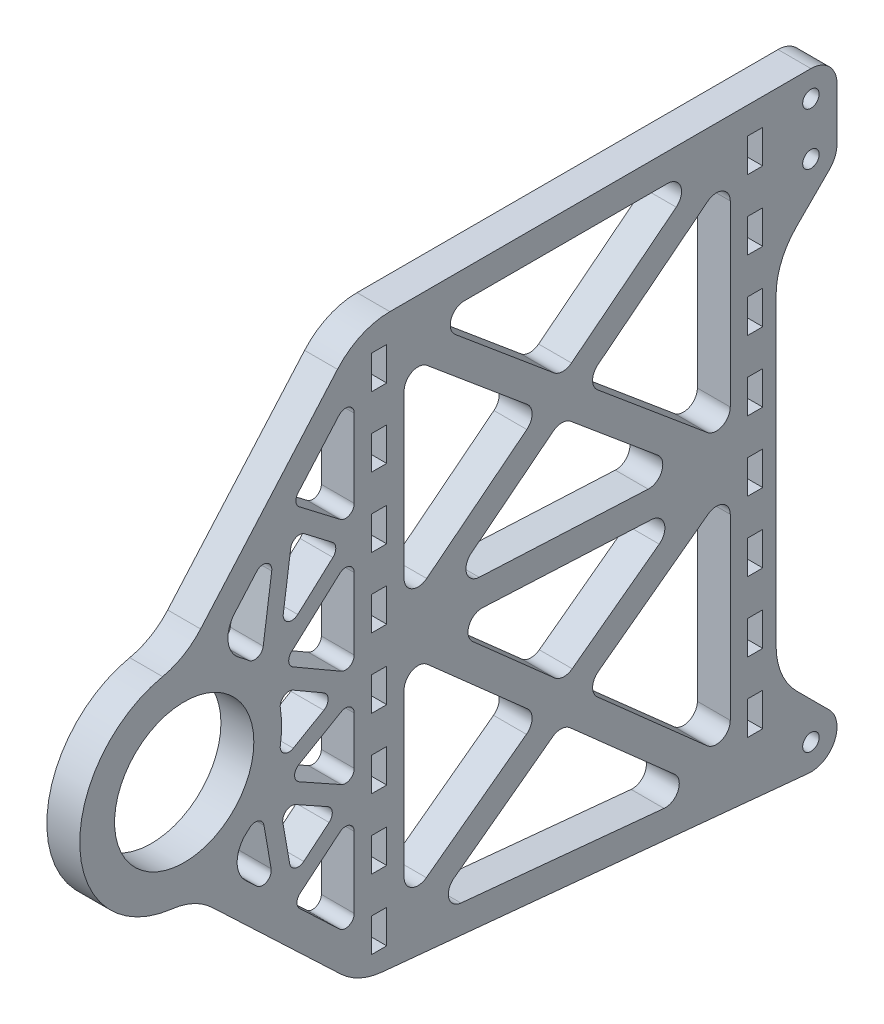
SolidWorks part; units mm, degrees
ref_plane "Front Plane" through (0, 0, 0) normal (0, 0, 1) x (1, 0, 0)
ref_plane "Top Plane" through (0, 0, 0) normal (0, 1, 0) x (1, 0, 0)
ref_plane "Right Plane" through (0, 0, 0) normal (1, 0, 0) x (0, 0, -1)
sketch "PlateGeometry" plane through (0, 0, 0) normal (1, 0, 0) x (0, 0, -1)
  line L1 (-38.1, -76.2) -> (38.1, -76.2) construction
  line L2 (-38.1, -76.2) -> (-38.1, 76.2) construction
  line L3 (-38.1, 76.2) -> (38.1, 76.2) construction
  line L4 (38.1, -76.2) -> (38.1, 76.2) construction
  line L5 (-38.1, -76.2) -> (38.1, 76.2) construction
  line L6 (-38.1, 76.2) -> (38.1, -76.2) construction
  line L11 (31.75, 76.2) -> (-31.75, 76.2) construction
  line L12 (31.75, 76.2) -> (31.75, -76.2) construction
  line L13 (31.75, -76.2) -> (-31.75, -76.2) construction
  line L14 (-31.75, 76.2) -> (-31.75, -76.2) construction
  line L15 (31.75, 76.2) -> (-31.75, -76.2) construction
  line L16 (31.75, -76.2) -> (-31.75, 76.2) construction
  point P0 (0, 0)
  point P9 (0, 0)
  line B0 (-35.7923, -66.6761) -> (-32.7923, -66.6739)
  line B1 (-35.7923, -66.6761) -> (-35.7877, -73.0261)
  line B2 (-35.7877, -73.0261) -> (-32.7877, -73.0239)
  line B3 (-32.7923, -66.6739) -> (-32.7877, -73.0239)
  line B4 (-35.7923, -66.6761) -> (-32.7877, -73.0239) construction
  line B5 (-35.7877, -73.0261) -> (-32.7923, -66.6739) construction
  line B6 (-35.7923, -53.9761) -> (-32.7923, -53.9739)
  line B7 (-35.7923, -53.9761) -> (-35.7877, -60.3261)
  line B8 (-35.7877, -60.3261) -> (-32.7877, -60.3239)
  line B9 (-32.7923, -53.9739) -> (-32.7877, -60.3239)
  line B10 (-35.7877, -60.3261) -> (-32.7923, -53.9739) construction
  line B11 (-35.7923, -41.2761) -> (-32.7923, -41.2739)
  line B12 (-35.7923, -41.2761) -> (-35.7877, -47.6261)
  line B13 (-35.7877, -47.6261) -> (-32.7877, -47.6239)
  line B14 (-32.7923, -41.2739) -> (-32.7877, -47.6239)
  line B15 (-35.7923, -41.2761) -> (-32.7877, -47.6239) construction
  line B16 (-35.7877, -47.6261) -> (-32.7923, -41.2739) construction
  line B17 (-35.7923, -28.5761) -> (-32.7923, -28.5739)
  line B18 (-35.7877, -34.9261) -> (-32.7877, -34.9239)
  line B19 (-32.7923, -28.5739) -> (-32.7877, -34.9239)
  line B20 (-35.7923, -15.8761) -> (-35.7877, -22.2261)
  line B21 (-32.7923, -15.8739) -> (-32.7877, -22.2239)
  line B22 (-35.7923, 9.5239) -> (-32.7923, 9.5261)
  line B23 (-32.7923, 9.5261) -> (-32.7877, 3.1761)
  line B24 (-35.7923, 9.5239) -> (-32.7877, 3.1761) construction
  line B25 (-35.7923, 22.2239) -> (-35.7877, 15.8739)
  line B26 (-35.7923, 34.9239) -> (-35.7877, 28.5739)
  line B27 (-35.7923, 47.6239) -> (-35.7877, 41.2739)
  line B28 (-35.7877, 41.2739) -> (-32.7923, 47.6261) construction
  line B29 (32.7886, -66.6757) -> (32.7914, -73.0257)
  line B30 (32.7914, -73.0257) -> (35.7914, -73.0243)
  line B31 (35.7886, -66.6743) -> (35.7914, -73.0243)
  line B32 (32.7886, -66.6757) -> (35.7914, -73.0243) construction
  line B33 (32.7914, -73.0257) -> (35.7886, -66.6743) construction
  line B34 (32.7886, -53.9757) -> (35.7886, -53.9743)
  line B35 (35.7886, -53.9743) -> (35.7914, -60.3243)
  line B36 (32.7914, -47.6257) -> (35.7914, -47.6243)
  line B37 (35.7886, -41.2743) -> (35.7914, -47.6243)
  line B38 (32.7886, -41.2757) -> (35.7914, -47.6243) construction
  line B39 (32.7886, -28.5757) -> (35.7914, -34.9243) construction
  line B40 (32.7886, -15.8757) -> (32.7914, -22.2257)
  line B41 (32.7886, -3.1757) -> (35.7914, -9.5243) construction
  line B42 (32.7914, -9.5257) -> (35.7886, -3.1743) construction
  line B43 (32.7886, 9.5243) -> (35.7886, 9.5257)
  line B44 (32.7886, 9.5243) -> (32.7914, 3.1743)
  line B45 (32.7914, 3.1743) -> (35.7914, 3.1757)
  line B46 (32.7886, 9.5243) -> (35.7914, 3.1757) construction
  line B47 (32.7886, 22.2243) -> (32.7914, 15.8743)
  line B48 (35.7886, 22.2257) -> (35.7914, 15.8757)
  line B49 (32.7886, 22.2243) -> (35.7914, 15.8757) construction
  line B50 (32.7914, 15.8743) -> (35.7886, 22.2257) construction
  line B51 (32.7914, 41.2743) -> (35.7914, 41.2757)
  line B52 (35.7886, 47.6257) -> (35.7914, 41.2757)
  line B53 (32.7886, 60.3243) -> (32.7914, 53.9743)
  line B54 (35.7886, 60.3257) -> (35.7914, 53.9757)
  line B55 (32.7886, 73.0243) -> (32.7914, 66.6743)
  line B56 (35.7886, 73.0257) -> (35.7914, 66.6757)
  line B57 (32.7914, 66.6743) -> (35.7886, 73.0257) construction
  circle B58 centre (-37.3063, -73.025) radius 5.5563 construction
  circle B59 centre (-37.3063, -73.025) radius 6.8263 construction
  circle B60 centre (-44.9262, -53.975) radius 5.5563 construction
  circle B61 centre (-44.9262, -53.975) radius 6.8263 construction
  dimension "D11" = 63.5
  dimension "D12" = 3.175
  dimension "D1" = 76.2
  dimension "D2" = 152.4
  dimension "D4" = 3.81
  dimension "D5" = 6.35
  dimension "D6" = 12.7
  dimension "D7" = 6.35
  dimension "D8" = 3.81
  dimension "D10" = 12.7
  dimension "D13" = 19.05
  dimension "D14" = 7.62
  dimension "D3" = 12
  dimension "D9" = 12
sketch_block_instance "SlotOutline-1"
sketch_block "SlotOutline" parameters "D1"=18.06, "D2"=7.2935
sketch_block_instance "SlotOutline-2"
sketch_block_instance "SlotOutline-3"
sketch_block_instance "SlotOutline-4"
sketch_block_instance "SlotOutline-5"
sketch_block_instance "SlotOutline-6"
sketch_block_instance "SlotOutline-7"
sketch_block_instance "SlotOutline-8"
sketch_block_instance "SlotOutline-9"
sketch_block_instance "SlotOutline-10"
sketch_block_instance "SlotOutline-11"
sketch_block_instance "SlotOutline-12"
sketch_block_instance "SlotOutline-13"
sketch_block_instance "SlotOutline-14"
sketch_block_instance "SlotOutline-15"
sketch_block_instance "SlotOutline-16"
sketch_block_instance "SlotOutline-17"
sketch_block_instance "SlotOutline-18"
sketch_block_instance "SlotOutline-19"
sketch_block_instance "SlotOutline-20"
sketch_block_instance "SlotOutline-21"
sketch_block_instance "SlotOutline-22"
sketch_block_instance "SlotOutline-23"
sketch_block_instance "SlotOutline-24"
sketch_block_instance "PulleyOutline-1"
sketch_block "PulleyOutline" parameters "D1"=11.1125, "D2"=13.6525
sketch_block_instance "PulleyOutline-2"
sketch "MotorGeometry" plane through (0, 0, 0) normal (1, 0, 0) x (0, 0, -1)
  line L0 (-83.2734, 1.775) -> (-83.2734, 49.025) construction
  line L3 (-50.2786, -55.4665) -> (-63.8121, -13.9087) construction
  line L4 (-41.2645, -76.9242) -> (-75.3216, -19.0975) construction
  line L5 (-38.1, -76.2) -> (-38.1, 76.2) construction
  line L6 (-38.1, -76.2) -> (38.1, -76.2) construction
  line L7 (38.1, -76.2) -> (38.1, 76.2) construction
  line L8 (-83.2734, 17.65) -> (-69.85, 9.9) construction
  line L9 (-69.85, 9.9) -> (-56.4266, 17.65) construction
  line L10 (-56.4266, 17.65) -> (-56.4266, 33.15) construction
  line L11 (-56.4266, 33.15) -> (-69.85, 40.9) construction
  line L12 (-69.85, 40.9) -> (-83.2734, 33.15) construction
  line L13 (-83.2734, 33.15) -> (-83.2734, 17.65) construction
  line L14 (-86.2734, 1.775) -> (-86.2734, 49.025)
  line L15 (-80.2734, 1.775) -> (-80.2734, 49.025)
  line L16 (-56.4266, 1.775) -> (-56.4266, 49.025) construction
  line L17 (-59.4266, 1.775) -> (-59.4266, 49.025)
  line L18 (-53.4266, 1.775) -> (-53.4266, 49.025)
  line L19 (-69.85, 8.3125) -> (-69.85, 47.25) construction
  line L20 (-72.85, 8.3125) -> (-72.85, 47.25)
  line L21 (-66.85, 8.3125) -> (-66.85, 47.25)
  circle A0 centre (44.45, -66.675) radius 1.5
  circle A1 centre (-69.85, -15.875) radius 11
  circle A5 centre (-69.85, -15.875) radius 30 construction
  circle A6 centre (-69.85, -15.875) radius 6.35 construction
  circle A7 centre (-44.9262, -53.975) radius 5.5562 construction
  circle A8 centre (-37.3063, -73.025) radius 5.5562 construction
  circle A9 centre (-69.85, -15.875) radius 25.5 construction
  circle A10 centre (-69.85, 25.4) radius 16 construction
  circle A11 centre (-69.85, 25.4) radius 11.5 construction
  circle A12 centre (-69.85, 25.4) radius 13.4234 construction
  arc A13 (-86.2734, 1.775) -> (-80.2734, 1.775) centre (-83.2734, 1.775) ccw
  arc A14 (-80.2734, 49.025) -> (-86.2734, 49.025) centre (-83.2734, 49.025) ccw
  arc A15 (-59.4266, 1.775) -> (-53.4266, 1.775) centre (-56.4266, 1.775) ccw
  arc A16 (-53.4266, 49.025) -> (-59.4266, 49.025) centre (-56.4266, 49.025) ccw
  arc A17 (-72.85, 8.3125) -> (-66.85, 8.3125) centre (-69.85, 8.3125) ccw
  arc A18 (-66.85, 47.25) -> (-72.85, 47.25) centre (-69.85, 47.25) ccw
  point P29 (-83.2734, 25.4)
  point P39 (-56.4266, 25.4)
  point P46 (-69.85, 27.7812)
  dimension "D1" = 22
  dimension "D4" = 60
  dimension "D5" = 12.7
  dimension "D7" = 4.5
  dimension "D8" = 32
  dimension "D9" = 4.5
  dimension "D13" = 3
  dimension "D3" = 6
  dimension "D2" = 31
  dimension "D6" = 38.1
  dimension "D10" = 31.75
  dimension "D11" = 9.525
  dimension "D12" = 6.35
  dimension "D14" = 15.875
  dimension "D15" = 1.5875
  dimension "D16" = 15.875
  dimension "D17" = 6.35
  dimension "D18" = 41.275
sketch "Sketch4" plane through (0, 0, 0) normal (1, 0, 0) x (0, 0, -1)
  line L0 (49.2125, 25.4) -> (49.2125, 34.925)
  line L1 (47.8176, 22.0324) -> (38.1, 12.3148)
  line L2 (-30.48, -50.8) -> (-38.1, -50.8) construction
  line L3 (-30.48, -50.8) -> (-30.48, -63.5) construction
  line L4 (-30.48, -63.5) -> (-38.1, -63.5) construction
  line L5 (-38.1, -50.8) -> (-38.1, -63.5) construction
  line L6 (-30.48, -50.8) -> (-38.1, -63.5) construction
  line L7 (-30.48, -63.5) -> (-38.1, -50.8) construction
  line L8 (38.1, 12.3148) -> (38.1, -53.5898)
  line L9 (38.1, -53.5898) -> (47.8176, -63.3074)
  line L10 (38.1, -76.2) -> (38.1, 76.2) construction
  line L11 (43.9929, -71.4155) -> (-38.1, -63.5)
  line L12 (-38.1, -63.5) -> (-68.2893, -34.861)
  line L13 (-70.0557, 3.1739) -> (-38.1, 39.6875)
  line L14 (-38.1, -76.2) -> (-38.1, 76.2) construction
  line L15 (-38.1, 39.6875) -> (44.45, 39.6875)
  line L17 (-83.2734, 1.775) -> (-83.2734, 58.55) construction
  line L18 (-86.2734, 1.775) -> (-86.2734, 58.55) construction
  line L19 (-80.2734, 1.775) -> (-80.2734, 58.55) construction
  line L20 (-69.85, 8.3125) -> (-69.85, 53.6) construction
  line L21 (-72.85, 8.3125) -> (-72.85, 53.6) construction
  line L22 (-66.85, 8.3125) -> (-66.85, 53.6) construction
  line L23 (-56.4266, 1.775) -> (-56.4266, 58.55) construction
  line L24 (-59.4266, 1.775) -> (-59.4266, 58.55) construction
  line L25 (-53.4266, 1.775) -> (-53.4266, 58.55) construction
  circle A0 centre (44.45, 25.4) radius 1.5
  circle A1 centre (44.45, 34.925) radius 1.5
  circle A2 centre (44.45, -66.675) radius 4.7625 construction
  circle A3 centre (44.45, 25.4) radius 4.7625 construction
  circle A4 centre (44.45, 34.925) radius 4.7625 construction
  circle A5 centre (-69.85, -15.875) radius 12.7
  arc A6 (43.9929, -71.4155) -> (47.8176, -63.3074) centre (44.45, -66.675) ccw
  circle A7 centre (-69.85, -15.875) radius 19.05
  arc A8 (47.8176, 22.0324) -> (49.2125, 25.4) centre (44.45, 25.4) ccw
  arc A9 (49.2125, 34.925) -> (44.45, 39.6875) centre (44.45, 34.925) ccw
  circle A10 centre (44.45, -66.675) radius 1.5
  arc A11 (-86.2734, 1.775) -> (-80.2734, 1.775) centre (-83.2734, 1.775) ccw construction
  arc A12 (-80.2734, 58.55) -> (-86.2734, 58.55) centre (-83.2734, 58.55) ccw construction
  arc A13 (-72.85, 8.3125) -> (-66.85, 8.3125) centre (-69.85, 8.3125) ccw construction
  arc A14 (-66.85, 53.6) -> (-72.85, 53.6) centre (-69.85, 53.6) ccw construction
  arc A15 (-59.4266, 1.775) -> (-53.4266, 1.775) centre (-56.4266, 1.775) ccw construction
  arc A16 (-53.4266, 58.55) -> (-59.4266, 58.55) centre (-56.4266, 58.55) ccw construction
  arc A17 (-72.85, 24.1875) -> (-66.85, 24.1875) centre (-69.85, 24.1875) cw construction
  arc A18 (-72.85, 33.3625) -> (-66.85, 33.3625) centre (-69.85, 33.3625) ccw construction
  point P12 (-34.29, -57.15)
  point P36 (-83.2734, 30.1625)
  point P41 (-65.6393, 2.7038)
  point P42 (-71.0229, -34.8889)
  point P47 (-69.85, 30.9562)
  point P55 (-56.4266, 30.1625)
  dimension "D1" = 3
  dimension "D4" = 9.525
  dimension "D9" = 25.4
  dimension "D10" = 38.1
  dimension "D11" = 6
  dimension "D14" = 3.175
  dimension "D2" = 9.525
  dimension "D3" = 101.6
  dimension "D5" = 3.81
  dimension "D6" = 12.7
  dimension "D7" = 45
  dimension "D8" = 45
  dimension "D12" = 12.7
  dimension "D13" = 25.4
  dimension "D15" = 15.875
extrude "Boss-Extrude1" add sketch "Sketch4" along normal mid plane 6 contours L0 A9 L13 A7 L12 L11 A6 L9 L8 L1 A8 A0 A1 | A7 A5 | L24 A15 L25 L13 | L13 A13 L22 region at (0, -13.2133, 6.0048) region at (0, -2.7151, 56.8315)
sketch "Sketch5" plane through (3, 0, 0) normal (1, 0, 0) x (0, 0, -1)
  line B0 (35.665, -54.102) -> (32.915, -54.102)
  line B1 (35.665, -54.102) -> (35.665, -60.198)
  line B2 (35.665, -60.198) -> (32.915, -60.198)
  line B3 (32.915, -54.102) -> (32.915, -60.198)
  line B4 (35.665, -54.102) -> (32.915, -60.198) construction
  line B5 (35.665, -60.198) -> (32.915, -54.102) construction
  line B6 (-32.915, -54.102) -> (-35.665, -54.102)
  line B7 (-32.915, -54.102) -> (-32.915, -60.198)
  line B8 (-32.915, -60.198) -> (-35.665, -60.198)
  line B9 (-35.665, -54.102) -> (-35.665, -60.198)
  line B10 (-32.915, -54.102) -> (-35.665, -60.198) construction
  line B11 (-32.915, -60.198) -> (-35.665, -54.102) construction
sketch_block_instance "Slot-1"
sketch_block "Slot" parameters "D1"=11.2845, "D2"=5.6739
sketch_block_instance "Slot-2"
extrude "LowerSlot" cut sketch "Sketch5" against normal through all both and the other way through all contours B0 B3 B2 B1 region at (3, -57.15, -34.29)
extrude "UpperSlot" cut sketch "Sketch5<3>" against normal through all both and the other way through all contours B6 B9 B8 B7 region at (3, -57.15, 34.29)
sketch "Sketch5<3>" plane through (3, 0, 0) normal (1, 0, 0) x (0, 0, -1) same geometry as "Sketch5"
pattern_linear "LowerSlots" count 8 spacing 12.7 along (0, 1, 0) of "LowerSlot"
pattern_linear "UpperSlots" count 8 spacing 12.7 along (0, 1, 0) of "UpperSlot"
sketch "Sketch6" plane through (3, 0, 0) normal (1, 0, 0) x (0, 0, -1)
  line L0 (-38.84, 7.4417) -> (-54.5614, -6.7982) construction
  line L1 (-54.5614, -6.7982) -> (-38.84, -15.875) construction
  line L2 (-38.84, -15.875) -> (-54.5614, -24.9518) construction
  line L3 (-54.5614, -24.9518) -> (-38.84, -33.7118) construction
  line L4 (-38.84, -15.875) -> (-52.07, -15.875) construction
  line L5 (-51.2473, 16.9514) -> (-54.5614, -6.7982) construction
  line L6 (-54.5614, -24.9518) -> (-51.2473, -44.0256) construction
  line L8 (29.74, -64.9377) -> (29.74, 34.6075)
  line L9 (-29.74, -59.2025) -> (-29.74, 34.6075)
  line L10 (-38.84, 31.1284) -> (-38.84, -55.7958)
  line L11 (-32.915, -54.102) -> (-32.915, -60.198) construction
  line L12 (-35.665, -54.102) -> (-35.665, -60.198) construction
  line L13 (32.915, -54.102) -> (32.915, -60.198) construction
  line L14 (29.74, -15.1651) -> (-29.74, -12.2975) construction
  line L15 (29.74, -64.9377) -> (-29.74, -12.2975) construction
  line L16 (44.1325, 25.5315) -> (44.1325, 34.6075)
  line L17 (44.1325, 34.6075) -> (-35.7952, 34.6075)
  line L18 (-35.7952, 34.6075) -> (-67.873, -2.0456)
  line L19 (-66.5997, -29.4616) -> (-35.8722, -58.6113)
  line L20 (-35.8722, -58.6113) -> (43.6001, -66.2741)
  line L21 (43.6001, -66.2741) -> (33.02, -55.694)
  line L22 (33.02, -55.694) -> (33.02, 14.419)
  line L23 (33.02, 14.419) -> (44.1325, 25.5315)
  line L24 (44.1325, 25.5315) -> (44.1325, 34.6075)
  line L25 (44.1325, 34.6075) -> (-35.7952, 34.6075)
  line L26 (-35.7952, 34.6075) -> (-67.873, -2.0456)
  line L27 (-66.5997, -29.4616) -> (-35.8722, -58.6113)
  line L28 (-35.8722, -58.6113) -> (43.6001, -66.2741)
  line L29 (43.6001, -66.2741) -> (33.02, -55.694)
  line L30 (33.02, -55.694) -> (33.02, 14.419)
  line L31 (33.02, 14.419) -> (44.1325, 25.5315)
  line L32 (-29.74, -12.2975) -> (29.74, 34.6075) construction
  line L33 (29.74, -15.1651) -> (-29.74, 34.6075) construction
  line L34 (-29.74, -59.2025) -> (29.74, -15.1651) construction
  line L35 (-51.2473, -44.0256) -> (-38.84, -33.7118) construction
  line L39 (-38.84, 7.4417) -> (-51.2473, 16.9514) construction
  line L44 (-56.695, -21.9456) -> (-52.3418, -46.9999)
  line L45 (-52.3418, -46.9999) -> (-36.0444, -33.4522)
  line L46 (-56.695, -21.9456) -> (-36.0444, -33.4522)
  line L47 (-55.3552, -8.1731) -> (-42.015, -15.875)
  line L48 (-42.015, -15.875) -> (-55.3552, -23.5769)
  line L49 (-52.4432, 19.8681) -> (-56.7383, -10.9119)
  line L50 (-36.363, 7.5434) -> (-52.4432, 19.8681)
  line L51 (-36.363, 7.5434) -> (-56.7383, -10.9119)
  line L52 (-52.4278, -27.9579) -> (-50.1528, -41.0514)
  line L53 (-50.1528, -41.0514) -> (-41.6356, -33.9713)
  line L54 (-52.4278, -27.9579) -> (-41.6356, -33.9713)
  line L55 (-53.7677, -5.4234) -> (-35.665, -15.875)
  line L56 (-35.665, -15.875) -> (-53.7677, -26.3266)
  line L57 (-50.0515, 14.0346) -> (-52.3845, -2.6846)
  line L58 (-41.317, 7.3401) -> (-50.0515, 14.0346)
  line L59 (-41.317, 7.3401) -> (-52.3845, -2.6846)
  line L60 (28.0566, -66.8398) -> (-31.4234, -14.1996)
  line L61 (-31.3128, -10.303) -> (28.1672, 36.602)
  line L62 (28.11, -17.113) -> (-31.37, 32.6595)
  line L63 (-31.2514, -57.1611) -> (28.2286, -13.1237)
  line L64 (29.6177, -17.7021) -> (-29.8623, -14.8346)
  line L65 (31.4234, -63.0356) -> (-28.0566, -10.3954)
  line L66 (-28.1672, -14.292) -> (31.3128, 32.613)
  line L67 (31.37, -13.2171) -> (-28.11, 36.5555)
  line L68 (-28.2286, -61.2439) -> (31.2514, -17.2065)
  line L69 (29.8623, -12.628) -> (-29.6177, -9.7605)
  arc A5 (-58.6124, -37.0388) -> (-58.3903, -29.4693) centre (-55.1161, -33.3533) cw
  circle A6 centre (-69.85, -15.875) radius 17.78
  circle A7 centre (-69.85, -15.875) radius 17.78
  arc A8 (-67.873, -2.0456) -> (-66.5997, -29.4616) centre (-69.85, -15.875) ccw
  arc A9 (-67.873, -2.0456) -> (-66.5997, -29.4616) centre (-69.85, -15.875) ccw
  arc A10 (-59.6996, -1.2771) -> (-60.6223, 6.2393) centre (-56.7995, 2.8937) cw
  point P18 (0, 0)
  point P41 (-51.2473, 16.9514)
  dimension "D6" = 5.08
  dimension "D2" = 3.175
  dimension "D3" = 3.175
  dimension "D4" = 3.175
  dimension "D7" = 60
  dimension "D1" = 5.08
  dimension "D5" = 5.08
  dimension "D8" = 1.5875
  dimension "D9" = 1.5875
  dimension "D10" = 2.54
  dimension "D11" = 2.54
extrude "Cut-Extrude1" cut sketch "Sketch6" against normal through all both and the other way through all contours L45 L27 L10 | L54 L52 L53 | L10 L56 L46 | A7 A5 L27 L44 | A7 L48 L47 | L51 L55 L10 | L59 L58 L57 | A10 A7 L49 L26 | L50 L10 L26 region at (3, -45.566, 42.5892) region at (3, -24.8433, 43.008) region at (3, -34.2808, 56.7363) region at (3, -5.0849, 43.1871) region at (3, 19.5729, 42.6265) region at (3, -15.875, 48.9797) region at (3, 4.3105, 57.3434) region at (3, -34.3269, 48.0721) region at (3, 6.23, 47.9176)
extrude "Cut-Extrude2" cut sketch "Sketch6<3>" against normal through all both and the other way through all contours L68 L28 L60 | L9 L63 L60 | L68 L65 L8 | L65 L63 L64 | L69 L62 L66 | L61 L62 L9 | L67 L8 L66 | L67 L61 L25 region at (3, -39.2947, -20.8764) region at (3, -55.0641, 0.5163) region at (3, -22.3709, 0.2933) region at (3, -36.4642, 21.4644) region at (3, 9.9735, -20.8752) region at (3, -5.0548, 0.4832) region at (3, 27.6489, 0.3262) region at (3, 10.9169, 21.4633)
sketch "Sketch6<3>" plane through (3, 0, 0) normal (1, 0, 0) x (0, 0, -1) same geometry as "Sketch6"
fillet "Fillet1" radius 1.5875 25 edges at (0, 9.4419, 38.84) (0, 31.1284, 38.84) (0, 18.1485, 50.1996) (0, 14.7725, 53.1543) (0, 7.3401, 41.317) (0, 14.0346, 50.0515) (0, -2.6846, 52.3845) (0, -6.5125, 51.8813) (0, -14.0419, 38.84) (0, 5.2998, 38.84) (0, -22.3955, 53.3088) (0, -15.875, 42.015) (0, -9.3545, 53.3088) (0, -42.1954, 53.1766) (0, -17.7081, 38.84) (0, -24.9272, 51.3439) (0, -31.8945, 38.84) (0, -27.9579, 52.4278) (0, -41.0514, 50.1528) (0, -33.9713, 41.6356) (0, -55.7958, 38.84) (0, -35.7761, 38.84) (0, -45.1259, 50.0875)
fillet "Fillet2" radius 2.54 24 edges at (0, 13.7316, 0.8346) (0, 34.6075, -25.638) (0, 34.6075, 25.7821) (0, -11.8531, -29.74) (0, 31.3727, -29.74) (0, 10.4009, -3.1457) (0, 10.5178, 4.9099) (0, 31.2955, 29.74) (0, -9.0628, 29.74) (0, -12.2642, -22.3154) (0, 7.1871, 0.9296) (0, -10.0874, 22.8354) (0, -34.5711, 0.7397) (0, -17.3594, -22.5076) (0, -15.1824, 22.6477) (0, -38.0127, -3.1491) (0, -61.5458, -29.74) (0, -18.3255, -29.74) (0, -56.0421, 29.74) (0, -37.6611, 4.9133) (0, -59.5667, 25.9632) (0, -64.5229, -25.4388) (0, -41.1027, 1.0245) (0, -15.6894, 29.74)
fillet "Fillet3" radius 12.7 6 edges at (0, 12.3148, -38.1) (0, -53.5898, -38.1) (0, 39.6875, 38.1) (0, 3.1739, 70.0557) (0, -34.861, 68.2893) (0, -63.5, 38.1)
